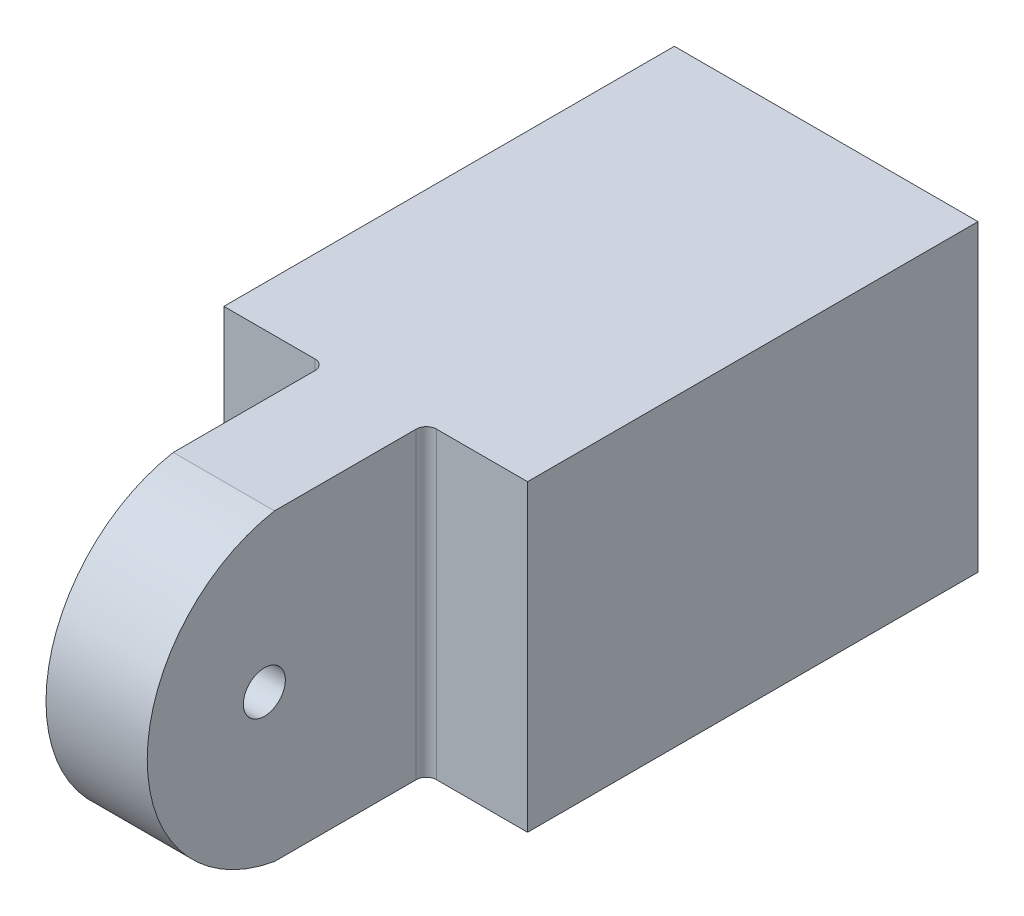
SolidWorks part; units mm, degrees
ref_plane "Front Plane" through (0, 0, 0) normal (0, 0, 1) x (1, 0, 0)
ref_plane "Top Plane" through (0, 0, 0) normal (0, 1, 0) x (1, 0, 0)
ref_plane "Right Plane" through (0, 0, 0) normal (1, 0, 0) x (0, 0, -1)
sketch "Sketch2" plane through (0, 0, 0) normal (0, 0, 1) x (1, 0, 0)
  line L1 (-30, 30) -> (30, 30)
  line L2 (-30, 30) -> (-30, -30)
  line L3 (-30, -30) -> (30, -30)
  line L4 (30, 30) -> (30, -30)
  line L5 (-30, 30) -> (30, -30) construction
  line L6 (-30, -30) -> (30, 30) construction
  point P0 (0, 0)
  dimension "D1" = 60
  dimension "D2" = 60
extrude "Boss-Extrude1" add sketch "Sketch2" along normal blind 89
ref_plane "Plane1" through (0, 0, 89) normal (0, 0, 1) x (1, 0, 0)
sketch "Sketch3" plane through (0, 0, 89) normal (0, 0, 1) x (1, 0, 0)
  line L0 (30, 30) -> (-30, 30) construction
  line L1 (10, -30) -> (-10, -30)
  line L2 (10, -30) -> (10, 30)
  line L3 (10, 30) -> (-10, 30)
  line L4 (-10, -30) -> (-10, 30)
  line L5 (10, -30) -> (-10, 30) construction
  line L6 (10, 30) -> (-10, -30) construction
  point P0 (0, 0)
  dimension "D1" = 20
extrude "Boss-Extrude2" add sketch "Sketch3" along normal blind 30
ref_plane "Plane2" through (10, 0, 0) normal (1, 0, 0) x (0, 0, -1)
sketch "Sketch4" plane through (10, 0, 0) normal (1, 0, 0) x (0, 0, -1)
  line L0 (-119, -30) -> (-119, 30)
  arc A0 (-119, -30) -> (-119, 30) centre (-113.6759, 0) cw
extrude "Boss-Extrude3" add sketch "Sketch4" against normal blind 20
fillet "Fillet1" radius 2 2 edges at (10, 0, 89) (-10, 0, 89)
ref_plane "Plane4" through (0, 0, 0) normal (0, 0, -1) x (-1, 0, 0)
sketch "Sketch7" plane through (0, 0, 0) normal (0, 0, -1) x (-1, 0, 0)
  line L0 (30, 30) -> (30, -30) construction
  line L1 (-25, 25) -> (25, 25)
  line L2 (-25, 25) -> (-25, -25)
  line L3 (-25, -25) -> (25, -25)
  line L4 (25, 25) -> (25, -25)
  line L5 (-25, 25) -> (25, -25) construction
  line L6 (-25, -25) -> (25, 25) construction
  line L7 (-30, 30) -> (30, 30) construction
  point P0 (0, 0)
  dimension "D1" = 5
  dimension "D2" = 5
extrude "Cut-Extrude1" cut sketch "Sketch7" against normal blind 81 contours L4 L3 L2 L1
ref_plane "Plane5" through (-10, 0, 0) normal (-1, 0, 0) x (0, 0, 1)
sketch "Sketch8" plane through (-10, 0, 0) normal (-1, 0, 0) x (0, 0, 1)
  line L0 (91, 30) -> (91, -30) construction
  circle A0 centre (121, 0) radius 4.15
  dimension "D1" = 8.3
  dimension "D2" = 30
extrude "Cut-Extrude2" cut sketch "Sketch8" against normal through all
